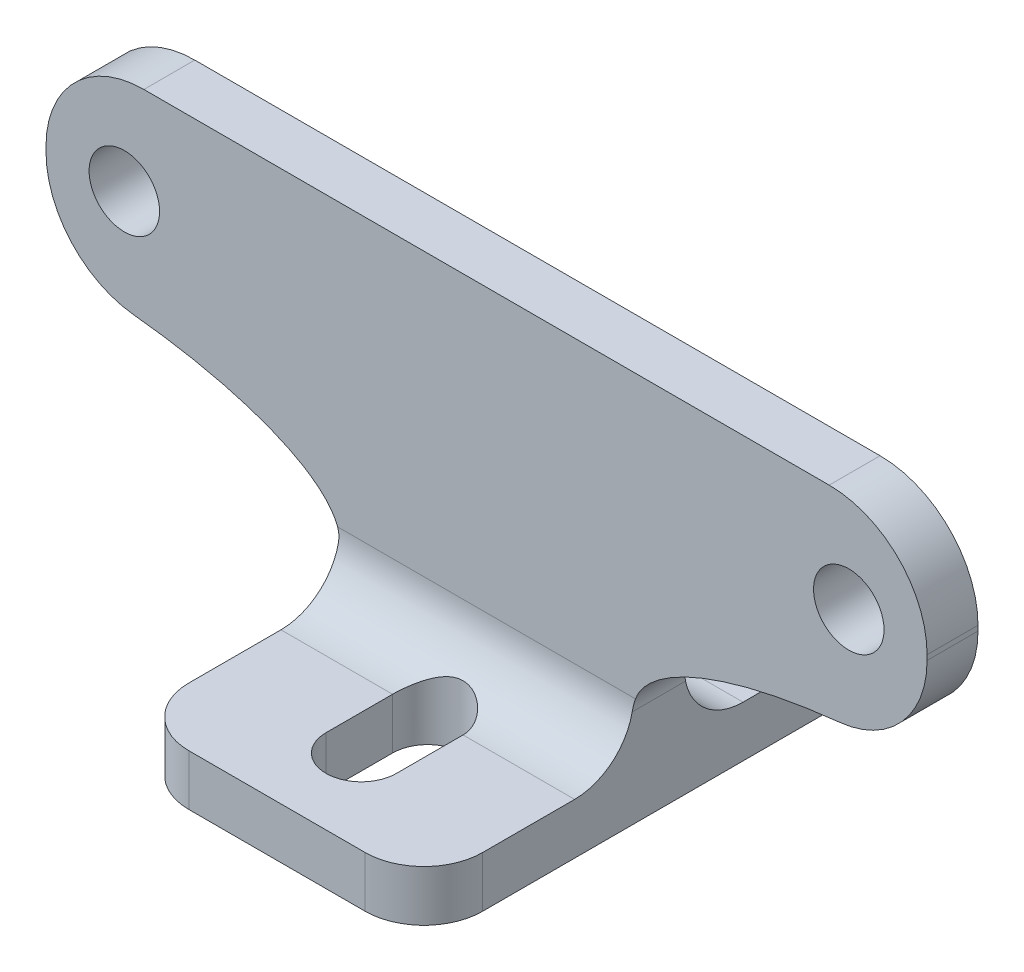
SolidWorks part; units mm, degrees
ref_plane "前视基准面" through (0, 0, 0) normal (0, 0, 1) x (1, 0, 0)
ref_plane "上视基准面" through (0, 0, 0) normal (0, 1, 0) x (1, 0, 0)
ref_plane "右视基准面" through (0, 0, 0) normal (1, 0, 0) x (0, 0, -1)
sketch "草图2" plane through (0, 0, 0) normal (0, 1, 0) x (1, 0, 0)
  line L1 (-7.5, 12) -> (7.5, 12)
  line L2 (-7.5, 12) -> (-7.5, 0)
  line L3 (-7.5, 0) -> (7.5, 0)
  line L4 (7.5, 12) -> (7.5, 0)
  dimension "D1" = 15
  dimension "D2" = 12
extrude "凸台-拉伸1" add sketch "草图2" along normal blind 2.6
sketch "草图5" plane through (0, 0, 0) normal (0, 0, 1) x (1, 0, 0)
  line L0 (0, 0) -> (0, -25.4003) construction
  line L1 (-7.5, 0) -> (7.5, 0)
  line L2 (-7.5, 0) -> (-7.5, 10)
  line L3 (-7.5, 10) -> (7.5, 10)
  line L4 (7.5, 0) -> (7.5, 10)
  line L9 (0, 0) -> (0, 36.4648) construction
  line L11 (-22.5, 20) -> (22.5, 20)
  line L12 (-22.5, 20) -> (-22.5, 10)
  line L13 (-22.5, 10) -> (22.5, 10)
  line L14 (22.5, 20) -> (22.5, 10)
  line L15 (-22.5, 20) -> (22.5, 10) construction
  line L16 (-22.5, 10) -> (22.5, 20) construction
  point P4 (0, 15)
  line M10 (7.5, 2.6) -> (-7.5, 2.6)
  dimension "D1" = 10
  dimension "D2" = 45
  dimension "D3" = 10
extrude "凸台-拉伸2" add sketch "草图5" against normal mid plane 2.6 contours L4 L3 L2 M10 | L13 L3 region at (0, 6.3, 0) region at (0, 15, 0)
mirror "镜向1" about plane through (-7.5, 2.6, 0) normal (0, 0, -1) of "凸台-拉伸1"
hole_wizard "M3 间隙槽口1" positions "草图14" profile "草图15" size "M3" standard "GB" slot yes end condition through all
sketch "草图14" plane through (0, 2.6, 0) normal (0, 1, 0) x (1, 0, 0)
  line L0 (0, -9.5) -> (0, -2.5) construction
  line L1 (7.5, -1.3) -> (7.5, -12) construction
  point P0 (0, -6)
  dimension "D1" = 7
  dimension "D2" = 7.5
  dimension "D3" = 6
sketch "草图15" plane through (0, 2.6, 6) normal (1, 0, 0) x (0, 0, 1)
  line L0 (0, 0) -> (0, 2.6)
  line L1 (0, 2.6) -> (1.8, 2.6)
  line L2 (1.8, 2.6) -> (1.8, 0)
  line L5 (1.8, 0) -> (0, 0)
  line L11 (0, -6.35) -> (0, 107.95) construction
  dimension "通孔孔直径" = 3.6
  dimension "通孔孔深度" = 2.6
mirror "镜向3" about plane through (0, 0, 0) normal (0, 0, 1) of "M3 间隙槽口1"
fillet "圆角6" radius 5 1 edges at (-7.5, 10, 0) second distance 15 first distance on face at (-7.5, 3.8, 0)
fillet "圆角10" radius 3 2 edges at (0, 2.6, 1.3) (0, 2.6, -1.3)
fillet "圆角11" radius 3 4 edges at (-7.5, 1.3, 12) (-7.5, 1.3, -12) (7.5, 1.3, -12) (7.5, 1.3, 12)
hole_wizard "M3 间隙孔3" positions "3D草图3" profile "草图16" hole size "M3" standard "GB" end condition through all
sketch3d "3D草图3"
  line L0 (0, 0, 0) -> (18.5, 15, 1.3) construction
  point P0 (18.5, 15, 1.3)
  dimension "D1" = 15
  dimension "D2" = 18.5
sketch "草图16" plane through (18.5, 15, 1.3) normal (1, 0, 0) x (0, -1, 0)
  line L0 (0, 0) -> (0, 13.3)
  line L1 (0, 13.3) -> (1.8, 13.3)
  line L2 (1.8, 13.3) -> (1.8, 0)
  line L5 (1.8, 0) -> (0, 0)
  line L11 (0, -6.35) -> (0, 107.95) construction
  dimension "通孔孔直径" = 3.6
  dimension "通孔孔深度" = 13.3
mirror "镜向5" about plane through (0, 0, 0) normal (1, 0, 0) of "M3 间隙孔3"
fillet "圆角12" radius 15 1 edges at (7.5, 10, 0) second distance 5 first distance on face at (15, 10, 0)
fillet "圆角13" radius 5 4 edges at (22.5, 20, 0) (-22.5, 20, 0)
